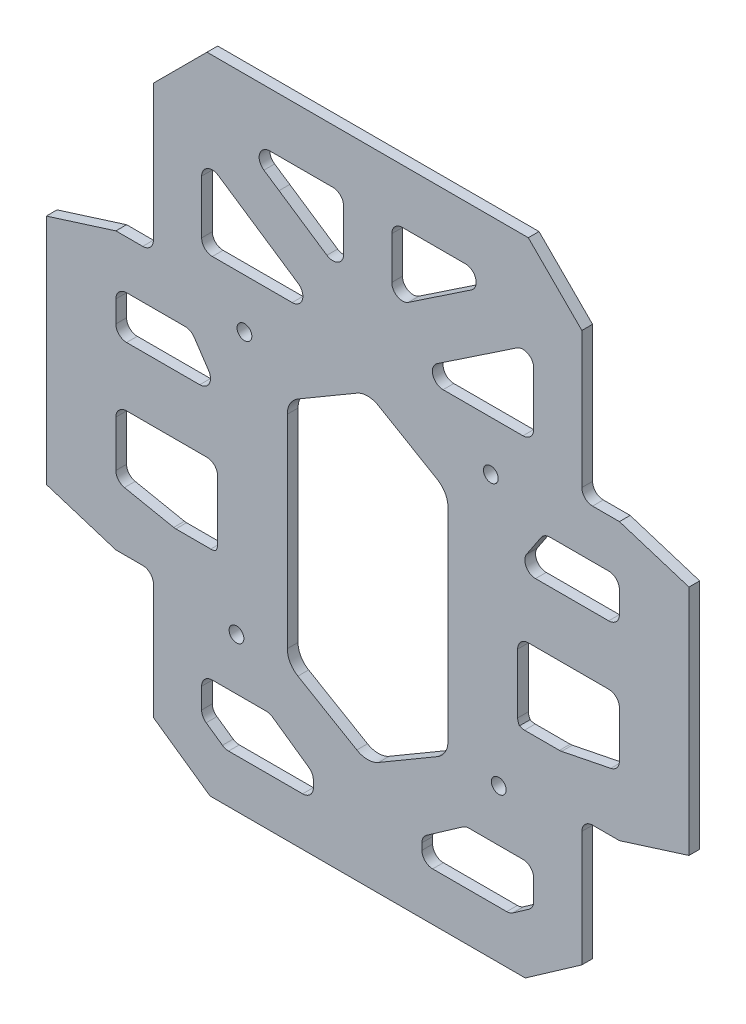
SolidWorks part; units mm, degrees
material "3.3549 (EN-AW 5182)"
ref_plane "Front Plane" through (0, 0, 0) normal (0, 0, 1) x (1, 0, 0)
ref_plane "Top Plane" through (0, 0, 0) normal (0, 1, 0) x (1, 0, 0)
ref_plane "Right Plane" through (0, 0, 0) normal (1, 0, 0) x (0, 0, -1)
sketch "Sketch1" plane through (0, 0, 0) normal (0, 0, 1) x (1, 0, 0)
  line L0 (0, 88.9) -> (0, -88.9) construction
  line L2 (-76.2, 63.5) -> (-76.2, -63.5)
  line L3 (-76.2, -63.5) -> (76.2, -63.5)
  line L4 (76.2, 63.5) -> (76.2, -63.5)
  line L5 (-76.2, 63.5) -> (76.2, -63.5) construction
  line L6 (-76.2, -63.5) -> (76.2, 63.5) construction
  line L7 (-50.8, 88.9) -> (50.8, 88.9)
  line L8 (-50.8, 88.9) -> (-76.2, 63.5)
  line L9 (50.8, 88.9) -> (76.2, 63.5)
  point P0 (0, 0)
  point P9 (0, 0)
  point P12 (0, 88.9)
  dimension "D1" = 127
  dimension "D2" = 152.4
extrude "Boss-Extrude1" add sketch "Sketch1" along normal mid plane 2.54
sketch "Sketch2" plane through (0, 0, 1.27) normal (0, 0, 1) x (1, 0, 0)
  line L0 (-88.4227, 63.5) -> (88.4227, 63.5) construction
  line L1 (0, 63.5) -> (0, -63.5) construction
  line L2 (-76.2, -63.5) -> (76.2, -63.5) construction
  line L5 (-19.05, 26.9875) -> (-19.05, -26.9875)
  line L7 (19.05, 26.9875) -> (19.05, -26.9875)
  line L8 (-19.05, 26.9875) -> (19.05, -26.9875) construction
  line L9 (-19.05, -26.9875) -> (19.05, 26.9875) construction
  line L12 (76.2, -63.5) -> (76.2, 63.5) construction
  line L20 (-19.05, -26.9875) -> (0, -38.1412)
  line L21 (0, -38.1412) -> (19.05, -26.9875)
  line L22 (-19.05, 26.9875) -> (0, 38.1412)
  line L23 (0, 38.1412) -> (19.05, 26.9875)
  line L25 (35.5785, -11.7583) -> (45.5484, -26.7132)
  line L27 (35.5785, 20.5149) -> (40.0764, 27.2618)
  line L28 (40.0764, 27.2618) -> (59.7085, 27.2618)
  line L29 (59.7085, 27.2618) -> (59.7085, -26.7132)
  line L30 (59.7085, -26.7132) -> (45.5484, -26.7132)
  line L31 (35.5785, 20.5149) -> (35.5785, -11.7583)
  line L38 (59.7085, -44.3116) -> (48.6284, -52.07)
  line L39 (48.6284, -52.07) -> (12.8735, -52.07)
  line L40 (12.8735, -52.07) -> (12.8735, -46.6599)
  line L41 (12.8735, -46.6599) -> (23.2228, -39.4132)
  line L42 (23.2228, -39.4132) -> (59.7085, -39.4132)
  line L43 (59.7085, -39.4132) -> (59.7085, -44.3116)
  line L44 (76.2, -63.5) -> (76.2, -57.785)
  line L45 (76.2, -57.785) -> (68.0381, -63.5)
  line L46 (68.0381, -63.5) -> (76.2, -63.5)
  line L47 (0, 88.9) -> (0, 73.66) construction
  line L48 (9.5435, 47.5818) -> (59.7085, 47.5818)
  line L50 (50.8, 88.9) -> (-50.8, 88.9) construction
  line L51 (59.7085, 47.5818) -> (59.7085, 58.1458)
  line L52 (59.7085, 58.1458) -> (46.5538, 72.39)
  line L53 (46.5538, 72.39) -> (9.5435, 47.5818)
  line L62 (-27.94, 73.66) -> (27.94, 73.66)
  line L63 (0, 54.9317) -> (27.94, 73.66)
  line L64 (-76.2, -57.785) -> (-68.0381, -63.5)
  line L65 (-76.2, -63.5) -> (-76.2, -57.785)
  line L66 (-68.0381, -63.5) -> (-76.2, -63.5)
  line L67 (-23.2228, -39.4132) -> (-59.7085, -39.4132)
  line L68 (-12.8735, -46.6599) -> (-23.2228, -39.4132)
  line L69 (-12.8735, -52.07) -> (-12.8735, -46.6599)
  line L70 (-48.6284, -52.07) -> (-12.8735, -52.07)
  line L71 (-59.7085, -44.3116) -> (-48.6284, -52.07)
  line L72 (-59.7085, -39.4132) -> (-59.7085, -44.3116)
  line L73 (-35.5785, 20.5149) -> (-40.0764, 27.2618)
  line L74 (-40.0764, 27.2618) -> (-59.7085, 27.2618)
  line L75 (-59.7085, 27.2618) -> (-59.7085, -26.7132)
  line L76 (-59.7085, -26.7132) -> (-45.5484, -26.7132)
  line L77 (-35.5785, -11.7583) -> (-45.5484, -26.7132)
  line L78 (-35.5785, 20.5149) -> (-35.5785, -11.7583)
  line L79 (-59.7085, 58.1458) -> (-46.5538, 72.39)
  line L80 (-59.7085, 47.5818) -> (-59.7085, 58.1458)
  line L81 (-9.5435, 47.5818) -> (-59.7085, 47.5818)
  line L82 (-46.5538, 72.39) -> (-9.5435, 47.5818)
  line L83 (0, 54.9317) -> (-27.94, 73.66)
  point P4 (0, 63.5)
  point P8 (0, 0)
  point P23 (35.56, 0)
  point P25 (35.56, 0)
  point P30 (59.69, 0)
extrude "Cut-Extrude2" cut sketch "Sketch2" against normal through all both and the other way through all
fillet "Fillet2" radius 3.81 7 edges at (-59.7085, 58.1458, 0) (-59.7085, 47.5818, 0) (59.7085, 47.5818, 0) (59.7085, 58.1458, 0) (0, 54.9317, 0) (46.5538, 72.39, 0) (-46.5538, 72.39, 0)
fillet "Fillet3" radius 2.54 4 edges at (27.94, 73.66, 0) (-27.94, 73.66, 0) (-9.5435, 47.5818, 0) (9.5435, 47.5818, 0)
fillet "Fillet5" radius 5.08 2 edges at (0, -38.1412, 0) (0, 38.1412, 0)
fillet "Fillet7" radius 5.08 4 edges at (-19.05, -26.9875, 0) (19.05, -26.9875, 0) (19.05, 26.9875, 0) (-19.05, 26.9875, 0)
fillet "Fillet8" radius 2.54 8 edges at (-23.2228, -39.4132, 0) (-48.6284, -52.07, 0) (-59.7085, -39.4132, 0) (-12.8735, -52.07, 0) (48.6284, -52.07, 0) (23.2228, -39.4132, 0) (12.8735, -52.07, 0) (59.7085, -39.4132, 0)
fillet "Fillet10" radius 2.54 4 edges at (12.8735, -46.6599, 0) (59.7085, -44.3116, 0) (-59.7085, -44.3116, 0) (-12.8735, -46.6599, 0)
fillet "Fillet11" radius 2.54 12 edges at (35.5785, -11.7583, 0) (45.5484, -26.7132, 0) (59.7085, -26.7132, 0) (59.7085, 27.2618, 0) (40.0764, 27.2618, 0) (35.5785, 20.5149, 0) (-59.7085, -26.7132, 0) (-45.5484, -26.7132, 0) (-59.7085, 27.2618, 0) (-35.5785, -11.7583, 0) (-35.5785, 20.5149, 0) (-40.0764, 27.2618, 0)
sketch "Sketch3" plane through (0, 0, -1.27) normal (0, 0, -1) x (-1, 0, 0)
  line L0 (0, 72.7013) -> (0, -72.7013) construction
  circle A0 centre (31.1008, -27.1643) radius 1.75
  circle A1 centre (29.2159, 35.8584) radius 1.75
  circle A2 centre (-31.1008, -27.1643) radius 1.75
  circle A3 centre (-29.2159, 35.8584) radius 1.75
  point P8 (0, 0)
  dimension "D1" = 3.5
  dimension "D2" = 3.5
extrude "Cut-Extrude4" cut sketch "Sketch3" against normal through all both and the other way through all
sketch "Sketch4" plane through (0, 0, -1.27) normal (0, 0, -1) x (-1, 0, 0)
  line L0 (0, 0) -> (0, -67.3984) construction
  line L2 (68.0381, -63.5) -> (-68.0381, -63.5) construction
  line L3 (-76.2, -52.07) -> (-76.2, -57.785)
  line L5 (76.2, 63.5) -> (76.2, -57.785) construction
  line L6 (76.2, -52.07) -> (59.7085, -63.5)
  line L7 (76.2, -52.07) -> (76.2, -57.785)
  line L8 (76.2, -57.785) -> (68.0381, -63.5)
  line L9 (68.0381, -63.5) -> (59.7085, -63.5)
  line L10 (-76.2, -57.785) -> (-68.0381, -63.5)
  line L11 (-68.0381, -63.5) -> (-59.7085, -63.5)
  line L12 (-76.2, -52.07) -> (-59.7085, -63.5)
extrude "Cut-Extrude5" cut sketch "Sketch4" against normal through all both and the other way through all
sketch "Sketch7" plane through (0, 0, -1.27) normal (0, 0, -1) x (-1, 0, 0)
  line L0 (35.5785, 19.7459) -> (59.7085, 19.7459)
  line L1 (59.7085, 24.7218) -> (59.7085, -24.1732) construction
  line L2 (59.7085, 19.7459) -> (59.7085, 9.5859)
  line L3 (59.7085, 9.5859) -> (35.5785, 9.5859)
  line L4 (35.5785, -10.9893) -> (35.5785, 19.7459) construction
  line L5 (35.5785, 9.5859) -> (35.5785, 19.7459)
  line L6 (39.3223, 26.1307) -> (47.4692, 38.351)
  line L7 (47.4692, 38.351) -> (59.7085, 38.351)
  line L8 (59.7085, 38.351) -> (59.7085, 24.7218)
  line L9 (59.7085, 24.7218) -> (39.3223, 26.1307)
  line L10 (0, 0) -> (0, 38.9156) construction
  line L11 (-59.7085, 9.5859) -> (-35.5785, 9.5859)
  line L12 (-59.7085, 19.7459) -> (-59.7085, 9.5859)
  line L13 (-35.5785, 19.7459) -> (-59.7085, 19.7459)
  line L14 (-35.5785, 9.5859) -> (-35.5785, 19.7459)
  line L15 (-59.7085, 38.351) -> (-59.7085, 24.7218)
  line L16 (-47.4692, 38.351) -> (-59.7085, 38.351)
  line L17 (-39.3223, 26.1307) -> (-47.4692, 38.351)
  line L18 (-59.7085, 24.7218) -> (-39.3223, 26.1307)
  dimension "D1" = 10.16
extrude "Cut-Extrude9" cut sketch "Sketch7" against normal through all both and the other way through all contours L9 L8 L7 L6 | L15 L18 L17 L16 region at (-51.4854, 31.3243, -1.27)
sketch "Sketch9" plane through (0, 0, -1.27) normal (0, 0, -1) x (-1, 0, 0)
  line L0 (35.5785, 19.7459) -> (59.7085, 19.7459)
  line L1 (59.7085, 38.351) -> (59.7085, -24.1732) construction
  line L2 (59.7085, 19.7459) -> (59.7085, 9.5859)
  line L3 (59.7085, 9.5859) -> (35.5785, 9.5859)
  line L4 (35.5785, -10.9893) -> (35.5785, 19.7459) construction
  line L5 (35.5785, 9.5859) -> (35.5785, 19.7459)
  line L6 (0, 0) -> (0, 23.9642) construction
  line L7 (-59.7085, 9.5859) -> (-35.5785, 9.5859)
  line L8 (-59.7085, 19.7459) -> (-59.7085, 9.5859)
  line L9 (-35.5785, 19.7459) -> (-59.7085, 19.7459)
  line L10 (-35.5785, 9.5859) -> (-35.5785, 19.7459)
extrude "Boss-Extrude4" add sketch "Sketch9" against normal up to surface (2.54 mm away) contours L7 L10 L9 L8 | L5 L0 L2 L3 region at (47.6435, 14.6659, -1.27) up to face at (45.9099, -0.9758, 1.27)
sketch "Sketch11" plane through (0, 0, -1.27) normal (0, 0, -1) x (-1, 0, 0)
  line L0 (-21.0031, 69.0101) -> (-31.5524, 76.0814)
  line L1 (21.0031, 69.0101) -> (31.5606, 76.069)
  line L2 (-31.5524, 76.0814) -> (31.5606, 76.069)
  line L3 (-21.0031, 69.0101) -> (21.0031, 69.0101)
extrude "Cut-Extrude10" cut sketch "Sketch11" against normal through all both and the other way through all
fillet "Fillet12" radius 2.54 2 edges at (-31.5606, 76.069, 0) (31.5524, 76.0814, 0)
sketch "Sketch12" plane through (0, 0, -1.27) normal (0, 0, -1) x (-1, 0, 0)
  line L0 (35.5785, 9.5859) -> (35.5785, 5.7001)
  line L1 (35.5785, -10.9893) -> (35.5785, 9.5859) construction
  line L2 (35.5785, 5.7001) -> (59.7085, 5.7001)
  line L3 (59.7085, 9.5859) -> (59.7085, -24.1732) construction
  line L4 (59.7085, 5.7001) -> (59.7085, 9.5859)
  line L5 (59.7085, 9.5859) -> (35.5785, 9.5859)
  line L6 (0, 0) -> (0, 71.0403) construction
  line L7 (-59.7085, 5.7001) -> (-59.7085, 9.5859)
  line L8 (-35.5785, 5.7001) -> (-59.7085, 5.7001)
  line L9 (-35.5785, 9.5859) -> (-35.5785, 5.7001)
  line L10 (-59.7085, 9.5859) -> (-35.5785, 9.5859)
extrude "Boss-Extrude5" add sketch "Sketch12" against normal up to surface (2.54 mm away) contours L4 L5 L0 L2 | L8 L7 L10 L9 region at (-47.6435, 7.643, -1.27) up to face at (-2.9991, 68.1599, 1.27)
fillet "Fillet13" radius 2.54 12 edges at (59.7085, 38.351, 0) (47.4692, 38.351, 0) (59.7085, 19.7459, 0) (35.5785, 19.7459, 0) (35.5785, 5.7001, 0) (59.7085, 5.7001, 0) (-59.7085, 38.351, 0) (-47.4692, 38.351, 0) (-59.7085, 19.7459, 0) (-59.7085, 5.7001, 0) (-35.5785, 5.7001, 0) (-35.5785, 19.7459, 0)
sketch "Sketch13" plane through (0, 0, -1.27) normal (0, 0, -1) x (-1, 0, 0)
  line L0 (-50.8, 88.9) -> (-50.8, 38.351)
  line L1 (-57.1685, 38.351) -> (-48.8285, 38.351) construction
  line L2 (-50.8, 38.351) -> (-76.2, 38.351)
  line L3 (-76.2, -52.07) -> (-76.2, 63.5) construction
  line L4 (-50.8, 88.9) -> (-76.2, 63.5)
  line L5 (-76.2, 63.5) -> (-76.2, 38.351)
  line L6 (0, 0) -> (0, 114.6984) construction
  line L7 (-112.9158, 0) -> (112.9158, 0) construction
  line L8 (50.8, 88.9) -> (76.2, 63.5)
  line L9 (50.8, 88.9) -> (50.8, 38.351)
  line L10 (50.8, 38.351) -> (76.2, 38.351)
  line L11 (76.2, 63.5) -> (76.2, 38.351)
  line L12 (-50.8, -63.5) -> (-50.8, -12.951)
  line L13 (59.7085, -63.5) -> (-59.7085, -63.5) construction
  line L14 (-50.8, -12.951) -> (-76.2, -12.951)
  line L15 (-76.2, -12.951) -> (-76.2, -52.07)
  line L16 (-76.2, -52.07) -> (-59.7085, -63.5)
  line L17 (-59.7085, -63.5) -> (-50.8, -63.5)
  line L18 (76.2, -52.07) -> (59.7085, -63.5)
  line L19 (76.2, -12.951) -> (76.2, -52.07)
  line L20 (50.8, -12.951) -> (76.2, -12.951)
  line L21 (50.8, -63.5) -> (50.8, -12.951)
  line L22 (59.7085, -63.5) -> (50.8, -63.5)
  point P16 (0, 0)
extrude "Cut-Extrude11" cut sketch "Sketch13" against normal through all
sketch "Sketch14" plane through (0, 0, -1.27) normal (0, 0, -1) x (-1, 0, 0)
  line L0 (-15.4135, -52.07) -> (-47.8275, -52.07) construction
  line L1 (50.8, -63.5) -> (-50.8, -63.5) construction
  line L2 (-50.8, -39.4132) -> (-43.8105, -39.4132)
  line L3 (-50.8, -39.4132) -> (-24.0237, -39.4132) construction
  line L4 (-43.8105, -39.4132) -> (-43.8105, -52.07)
  line L5 (-43.8105, -52.07) -> (-50.8, -52.07)
  line L6 (-50.8, -63.5) -> (-50.8, -50.5494) construction
  line L7 (-50.8, -52.07) -> (-50.8, -39.4132)
  line L8 (0, 115.1146) -> (0, -115.1146) construction
  line L9 (-22.5668, -39.8726) -> (-13.9566, -45.9015) construction
  line L10 (-43.8105, -45.0434) -> (-33.7755, -52.07)
  line L11 (-33.7755, -52.07) -> (-43.8105, -52.07)
  line L12 (-43.8105, -45.0434) -> (-43.8105, -52.07)
  line L13 (43.8105, -52.07) -> (50.8, -52.07)
  line L14 (43.8105, -39.4132) -> (43.8105, -52.07)
  line L15 (50.8, -39.4132) -> (43.8105, -39.4132)
  line L16 (50.8, -52.07) -> (50.8, -39.4132)
  line L17 (43.8105, -45.0434) -> (43.8105, -52.07)
  line L18 (43.8105, -45.0434) -> (33.7755, -52.07)
  line L19 (33.7755, -52.07) -> (43.8105, -52.07)
  point P17 (0, 0)
  dimension "D1" = 11.43
  dimension "D2" = 145
  dimension "D3" = 145
extrude "Boss-Extrude6" add sketch "Sketch14" against normal up to surface (2.54 mm away) contours L7 L2 L4 L5 | L11 L10 L12 | L13 L16 L15 L14 | L19 L18 L17 up to face at (0, 2.9347, 1.27)
sketch "Sketch15" plane through (0, 0, -1.27) normal (0, 0, -1) x (-1, 0, 0)
  line L2 (-39.37, -39.4132) -> (-39.37, -48.1527)
  line L3 (-43.8105, -39.4132) -> (-24.0237, -39.4132) construction
  line L4 (-43.8105, -45.0434) -> (-33.7755, -52.07) construction
  line L6 (-39.37, -39.4132) -> (-43.8105, -39.4132)
  line L7 (-43.8105, -39.4132) -> (-43.8105, -45.0434)
  line L8 (-43.8105, -45.0434) -> (-39.37, -48.1527)
  line L9 (0, 89.3741) -> (0, -89.3741) construction
  line L10 (43.8105, -39.4132) -> (43.8105, -45.0434)
  line L11 (39.37, -39.4132) -> (43.8105, -39.4132)
  line L12 (39.37, -39.4132) -> (39.37, -48.1527)
  line L13 (43.8105, -45.0434) -> (39.37, -48.1527)
  point P14 (0, 0)
extrude "Boss-Extrude7" add sketch "Sketch15" against normal up to surface (2.54 mm away) contours L8 L2 L6 L7 | L10 L13 L12 L11 up to face at (24.6987, -45.7308, 1.27)
fillet "Fillet15" radius 2.54 6 edges at (-33.7755, -52.07, 0) (-39.37, -48.1527, 0) (-39.37, -39.4132, 0) (33.7755, -52.07, 0) (39.37, -48.1527, 0) (39.37, -39.4132, 0)
sketch "Sketch16" plane through (0, 0, -1.27) normal (0, 0, -1) x (-1, 0, 0)
  line L0 (50.8, -54.1027) -> (37.3793, -63.5)
  line L1 (50.8, -26.7132) -> (50.8, -63.5) construction
  line L2 (50.8, -63.5) -> (-50.8, -63.5) construction
  line L4 (50.8, -54.1027) -> (50.8, -63.5)
  line L5 (50.8, -63.5) -> (37.3793, -63.5)
  line L6 (0, 0) -> (0, -107.7919) construction
  line L7 (-50.8, -54.1027) -> (-50.8, -63.5)
  line L8 (-50.8, -54.1027) -> (-37.3793, -63.5)
  line L9 (-50.8, -63.5) -> (-37.3793, -63.5)
extrude "Cut-Extrude12" cut sketch "Sketch16" against normal through all
sketch "Sketch17" plane through (0, 0, -1.27) normal (0, 0, -1) x (-1, 0, 0)
  line L3 (-76.2, -7.7512) -> (-59.7085, -12.951)
  line L4 (-76.2, -12.951) -> (-76.2, 38.351) construction
  line L5 (-76.2, -7.7512) -> (-76.2, -12.951)
  line L6 (-76.2, -12.951) -> (-59.7085, -12.951)
  line L7 (-76.2, 12.7) -> (87.8562, 12.7) construction
  line L8 (-59.7085, -12.951) -> (-50.8, -12.951)
  line L9 (-50.8, -12.951) -> (-50.8, -26.7132)
  line L10 (0, 0) -> (0, 94.9159) construction
  line L11 (76.2, -7.7512) -> (76.2, -12.951)
  line L12 (76.2, -7.7512) -> (59.7085, -12.951)
  line L13 (76.2, -12.951) -> (59.7085, -12.951)
  line L14 (76.2, 33.1512) -> (59.7085, 38.351)
  line L15 (76.2, 38.351) -> (59.7085, 38.351)
  line L16 (76.2, 33.1512) -> (76.2, 38.351)
  line L17 (-76.2, 33.1512) -> (-76.2, 38.351)
  line L18 (-76.2, 33.1512) -> (-59.7085, 38.351)
  line L19 (-76.2, 38.351) -> (-59.7085, 38.351)
  dimension "D1" = 107.5
extrude "Cut-Extrude13" cut sketch "Sketch17" against normal through all contours L17 L19 L18 | L14 L15 L16 | L11 L13 L12 | L6 L3 L5
sketch "Sketch18" plane through (0, 0, -1.27) normal (0, 0, -1) x (-1, 0, 0)
  line L0 (-59.7085, -12.951) -> (-59.7085, -24.127)
  line L1 (-76.2, -7.7512) -> (-76.2, -18.9272)
  line L2 (-76.2, -18.9272) -> (-59.7085, -24.127)
  line L3 (-76.2, -7.7512) -> (-59.7085, -12.951)
  line L4 (0, 0) -> (0, 95.1302) construction
  line L5 (-59.7085, 38.351) -> (-59.7085, 41.399)
  line L6 (-76.2, 33.1512) -> (-76.2, 36.1992)
  line L7 (-76.2, 36.1992) -> (-59.7085, 41.399)
  line L8 (-59.7085, 38.351) -> (-76.2, 33.1512)
  line L9 (76.2, -7.7512) -> (76.2, -18.9272)
  line L10 (76.2, -18.9272) -> (59.7085, -24.127)
  line L11 (59.7085, -12.951) -> (59.7085, -24.127)
  line L12 (76.2, -7.7512) -> (59.7085, -12.951)
  line L13 (59.7085, 38.351) -> (59.7085, 41.399)
  line L14 (76.2, 36.1992) -> (59.7085, 41.399)
  line L15 (76.2, 33.1512) -> (76.2, 36.1992)
  line L16 (59.7085, 38.351) -> (76.2, 33.1512)
  dimension "D1" = 11.176
  dimension "D2" = 3.048
extrude "Boss-Extrude8" add sketch "Sketch18" against normal up to surface (2.54 mm away) contours L3 L0 L2 L1 | L8 L6 L7 L5 | L13 L14 L15 L16 | L9 L10 L11 L12 up to face at (26.9142, -46.2965, 1.27)
sketch "Sketch19" plane through (0, 0, -1.27) normal (0, 0, -1) x (-1, 0, 0)
  line L0 (-50.8, -26.7132) -> (-50.8, -20.5461) construction
  line L1 (-59.7085, -24.127) -> (-50.8, -24.127)
  line L2 (-50.8, -24.127) -> (-50.8, -26.7132)
  line L3 (-59.7085, -24.127) -> (-59.7085, -12.697)
  line L4 (-59.7085, -24.127) -> (-59.7085, 3.1601) construction
  line L5 (-59.7085, -12.697) -> (-36.2042, -12.697)
  line L6 (-36.0051, -12.3982) -> (-44.7943, -25.5822) construction
  line L7 (-36.2042, -12.697) -> (-36.2042, -26.7132)
  line L8 (-36.2042, -26.7132) -> (-50.8, -26.7132)
  line L9 (-59.7085, 41.399) -> (-41.8812, 41.399)
  line L11 (-41.8812, 41.399) -> (-41.8812, 29.969)
  line L12 (-41.8812, 29.969) -> (-59.7085, 29.969)
  line L13 (-59.7085, 22.2859) -> (-59.7085, 35.811) construction
  line L14 (-59.7085, 29.969) -> (-59.7085, 41.399)
  line L15 (-50.8, 47.5818) -> (-39.37, 47.5818)
  line L16 (-17.8946, 47.5818) -> (-50.8, 47.5818) construction
  line L19 (-50.8, 47.5818) -> (-50.8, 71.2815)
  line L20 (-50.8, 67.7921) -> (-50.8, 88.9) construction
  line L21 (-50.8, 71.2815) -> (-39.37, 71.2815)
  line L22 (-39.37, 71.2815) -> (-39.37, 47.5818)
  line L23 (-46.7151, 37.2199) -> (-37.6984, 23.6948) construction
  line L24 (0, 0) -> (0, 103.7773) construction
  line L25 (36.2042, -12.697) -> (36.2042, -26.7132)
  line L26 (59.7085, -12.697) -> (36.2042, -12.697)
  line L27 (59.7085, -24.127) -> (59.7085, -12.697)
  line L28 (59.7085, -24.127) -> (50.8, -24.127)
  line L29 (50.8, -24.127) -> (50.8, -26.7132)
  line L30 (36.2042, -26.7132) -> (50.8, -26.7132)
  line L31 (41.8812, 29.969) -> (59.7085, 29.969)
  line L32 (41.8812, 41.399) -> (41.8812, 29.969)
  line L33 (59.7085, 41.399) -> (41.8812, 41.399)
  line L34 (59.7085, 29.969) -> (59.7085, 41.399)
  line L35 (50.8, 71.2815) -> (39.37, 71.2815)
  line L36 (50.8, 47.5818) -> (50.8, 71.2815)
  line L37 (50.8, 47.5818) -> (39.37, 47.5818)
  line L38 (39.37, 71.2815) -> (39.37, 47.5818)
extrude "Boss-Extrude9" add sketch "Sketch19" against normal up to surface (2.54 mm away) contours L22 L15 L19 L21 | L14 L9 L11 L12 | L35 L38 L37 L36 | L31 L34 L33 L32 | L25 L30 L29 L28 L27 L26 | L8 L2 L1 L3 L5 L7 up to face at (26.9142, -46.2965, 1.27)
sketch "Sketch20" plane through (0, 0, -1.27) normal (0, 0, -1) x (-1, 0, 0)
  line L0 (50.8, 88.9) -> (50.8, 76.2)
  line L2 (0, 0) -> (0, 93.8067) construction
  line L3 (-50.8, 88.9) -> (-50.8, 76.2)
  line L4 (-50.8, 41.399) -> (-50.8, 88.9) construction
  line L5 (-50.8, 88.9) -> (-38.1, 88.9)
  line L6 (-50.8, 88.9) -> (50.8, 88.9) construction
  line L7 (-50.8, 76.2) -> (-38.1, 88.9)
  line L8 (50.8, 88.9) -> (38.1, 88.9)
  line L9 (50.8, 76.2) -> (38.1, 88.9)
extrude "Cut-Extrude14" cut sketch "Sketch20" against normal through all
sketch "Sketch21" plane through (0, 0, -1.27) normal (0, 0, -1) x (-1, 0, 0)
  line L0 (-23.1983, 76.0798) -> (23.1948, 76.0707) construction
  line L2 (-5.7167, 54.4863) -> (5.7133, 54.4863)
  line L3 (-5.7167, 76.0763) -> (5.7133, 76.0741)
  line L4 (-5.7167, 76.0763) -> (-5.7167, 54.4863)
  line L5 (5.7133, 54.4863) -> (5.7133, 76.0741)
  point P4 (0, 0)
  point P8 (-0.0017, 76.0752)
  point P11 (-0.0017, 76.0752)
extrude "Boss-Extrude11" add sketch "Sketch21" against normal up to surface (2.54 mm away) contours L5 L3 L4 L2 up to face at (0, 9.9313, 1.27)
sketch "Sketch22" plane through (0, 0, -1.27) normal (0, 0, -1) x (-1, 0, 0)
  line L2 (-50.8, -24.127) -> (-50.8, 11.0964) construction
  line L3 (-45.7385, -12.697) -> (-59.7085, -9.8882)
  line L4 (-59.7085, -12.697) -> (-36.2042, -12.697) construction
  line L5 (-59.7085, -12.697) -> (-59.7085, 3.1601) construction
  line L7 (-59.7085, -9.8882) -> (-59.7085, -12.697)
  line L8 (-59.7085, -12.697) -> (-45.7385, -12.697)
  line L9 (0, 0) -> (0, -79.1388) construction
  line L10 (59.7085, -9.8882) -> (59.7085, -12.697)
  line L11 (45.7385, -12.697) -> (59.7085, -9.8882)
  line L12 (59.7085, -12.697) -> (45.7385, -12.697)
extrude "Boss-Extrude13" add sketch "Sketch22" against normal up to surface (2.54 mm away) contours L8 L3 L7 | L10 L12 L11 up to face at (15.242, 70.7185, 1.27)
fillet "Fillet16" radius 2.54 18 edges at (36.2042, -12.697, 0) (-36.2042, -12.697, 0) (-59.7085, -9.8882, 0) (-45.7385, -12.697, 0) (-59.7085, 29.969, 0) (-41.8812, 29.969, 0) (5.7167, 76.0763, 0) (5.7167, 58.7636, 0) (-5.7133, 76.0741, 0) (-5.7133, 58.7613, 0) (-39.37, 67.5747, 0) (-39.37, 47.5818, 0) (45.7385, -12.697, 0) (59.7085, -9.8882, 0) (41.8812, 29.969, 0) (59.7085, 29.969, 0) (39.37, 47.5818, 0) (39.37, 67.5747, 0)
fillet "Fillet17" radius 2.54 4 edges at (-50.8, 41.399, 0) (-50.8, -24.127, 0) (50.8, -24.127, 0) (50.8, 41.399, 0)
